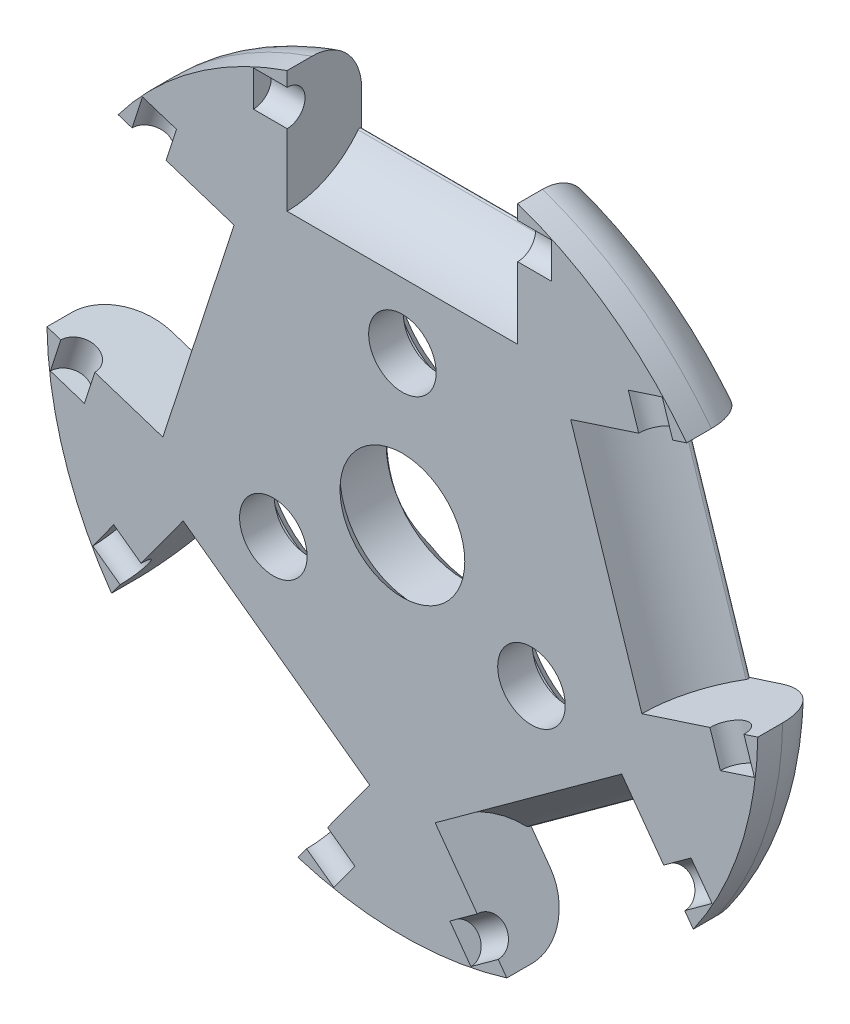
SolidWorks part; units mm, degrees
other "Markup1"
sketch "Sketch8" plane through (32.7336, 32.7336, 0) normal (0.5701, 0.1846, 0.8006) x (0.8043, 0.0736, -0.5897)
ref_plane "Front Plane" through (0, 0, 0) normal (0, 0, 1) x (1, 0, 0)
ref_plane "Top Plane" through (0, 0, 0) normal (0, 1, 0) x (1, 0, 0)
ref_plane "Right Plane" through (0, 0, 0) normal (1, 0, 0) x (0, 0, -1)
sketch "Sketch1" plane through (0, 0, 0) normal (0, 0, 1) x (1, 0, 0)
  circle A0 centre (0, 0) radius 22.7203
  dimension "D1" = 45.4406
extrude "Boss-Extrude2" add sketch "Sketch1" against normal blind 4.7625
fillet "Fillet1" radius 3.175 1 edges at (22.7203, 0, -4.7625)
sketch "Sketch2" plane through (0, 0, 0) normal (0, 0, 1) x (1, 0, 0)
  line L1 (-12.7, 22.7203) -> (12.7, 22.7203) construction
  line L2 (-7.366, 23.9903) -> (7.366, 23.9903)
  line L3 (-7.366, 23.9903) -> (-7.366, 13.5763)
  line L4 (-7.366, 13.5763) -> (7.366, 13.5763)
  line L5 (7.366, 23.9903) -> (7.366, 13.5763)
  line L6 (-7.366, 23.9903) -> (7.366, 13.5763) construction
  line L7 (-7.366, 13.5763) -> (7.366, 23.9903) construction
  line L35 (0, 0) -> (0, 22.7203) construction
  circle A1 centre (0, 0) radius 22.7203 construction
  point P10 (0, 18.7833)
  circle M7 centre (0, 0) radius 22.7203
  dimension "D1" = 14.732
  dimension "D2" = 10.414
  dimension "D3" = 1.27
  dimension "D4" = 25.4
extrude "Cut-Extrude2" cut sketch "Sketch2" against normal blind 12.7 contours L5 L3 L4 M7 | L3 L2 L5 L4 region at (0, 17.9536, 0)
pattern_circular "CirPattern1" count 5 over 360 about axis through (0, 0, 0) along (0, 0, 1) of "Cut-Extrude2"
ref_plane "Plane1" through (0, 0, 0) normal (1, 0, 0) x (0, 0, -1)
sketch "Sketch4" plane through (0, 0, 0) normal (1, 0, 0) x (0, 0, -1)
  line L0 (4.7625, 13.5763) -> (0, 13.5763) construction
  circle A0 centre (0, 19.4183) radius 1.143
  dimension "D1" = 2.286
  dimension "D2" = 5.842
extrude "Cut-Extrude4" cut sketch "Sketch4" against normal mid plane 19.05
pattern_circular "CirPattern2" count 5 over 360 about axis through (0, 0, 0) along (0, 0, 1) of "Cut-Extrude4"
sketch "Sketch5" plane through (0, 0, 0) normal (0, 0, 1) x (1, 0, 0)
  circle A0 centre (0, 0) radius 3.9688
  dimension "D1" = 7.9375
extrude "Cut-Extrude5" cut sketch "Sketch5" against normal through all
sketch "Sketch6" plane through (0, 0, -4.7625) normal (0, 0, -1) x (-1, 0, 0)
  circle A0 centre (0, 9.525) radius 2.159
  circle A1 centre (8.2489, -4.7625) radius 2.159
  circle A2 centre (-8.2489, -4.7625) radius 2.159
  point P4 (5.6715, -8.3641)
  point P5 (0, 0)
  point P9 (0, 0)
  dimension "D3" = 3
  dimension "D1" = 4.318
  dimension "D2" = 9.525
extrude "Cut-Extrude7" cut sketch "Sketch6" against normal through all
sketch "Sketch10" plane through (7.366, 0, 0) normal (-1, 0, 0) x (0, 0, 1)
  line L0 (-4.7625, 18.1042) -> (-4.7625, 13.5763) construction
  line L1 (-4.7625, 13.5763) -> (0, 13.5763)
  line L2 (-4.7625, 13.5763) -> (-4.7625, 16.2592)
  line L4 (0, 13.5763) -> (0, 13.7033)
  arc A0 (-4.7625, 16.2592) -> (0, 13.7033) centre (0, 19.4183) ccw
  dimension "D1" = 11.43
  dimension "D2" = 4.7625
extrude "Boss-Extrude4" add sketch "Sketch10" along normal up to next
fillet "Fillet2" radius 0.127 1 edges at (0, 16.2592, -4.7625)
pattern_circular "CirPattern5" count 5 over 360 about axis through (0, 0, 0) along (0, 0, 1) of "Boss-Extrude4", "Fillet2"
sketch "Sketch7" plane through (0, 0, -4.7625) normal (0, 0, -1) x (-1, 0, 0)
  circle A1 centre (8.2489, -4.7625) radius 4.445
  circle A2 centre (-8.2489, -4.7625) radius 4.445
  circle A3 centre (0, 9.525) radius 4.445
  point P0 (8.2489, -4.7625)
  point P12 (-8.2489, -4.272)
  dimension "D2" = 8.89
extrude "Cut-Extrude8" cut sketch "Sketch7" against normal blind 2.54
sketch "Sketch12" plane through (0, 0, -4.7625) normal (0, 0, -1) x (-1, 0, 0)
  circle A0 centre (0, 0) radius 5.0038
  dimension "D1" = 10.0076
extrude "Cut-Extrude9" cut sketch "Sketch12" against normal blind 3.9878
chamfer "Chamfer1" distance 0.7937 angle 45 1 edges at (-3.9688, 0, -0.7747)
chamfer "Chamfer2" distance 0.7937 angle 45 4 edges at (-12.6939, -4.7625, -4.7625) (3.8039, -4.7625, -4.7625) (-4.445, 9.525, -4.7625) (-5.0038, 0, -4.7625)
